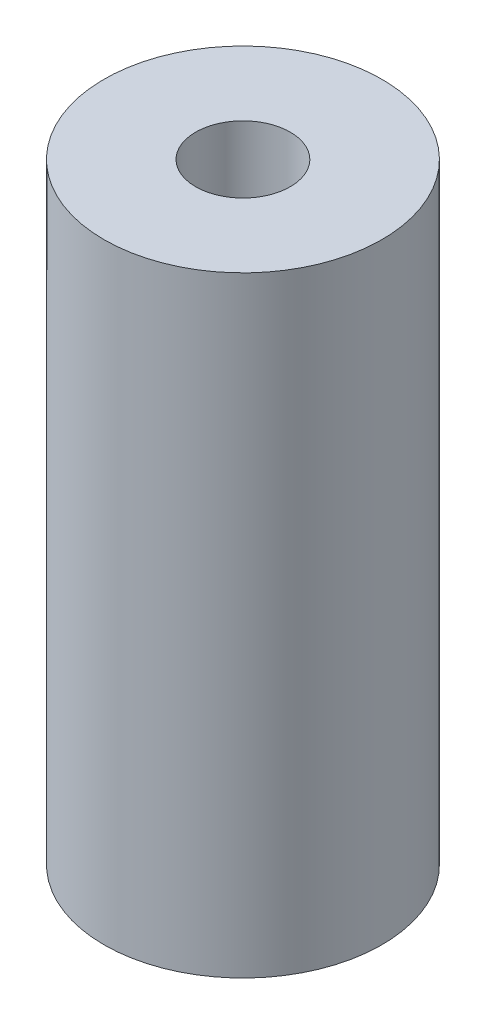
SolidWorks part; units mm, degrees
ref_plane "Front Plane" through (0, 0, 0) normal (0, 0, 1) x (1, 0, 0)
ref_plane "Top Plane" through (0, 0, 0) normal (0, 1, 0) x (1, 0, 0)
ref_plane "Right Plane" through (0, 0, 0) normal (1, 0, 0) x (0, 0, -1)
sketch "Sketch1" plane through (0, 0, 0) normal (0, 1, 0) x (1, 0, 0)
  circle A0 centre (0, 0) radius 1.55
  circle A1 centre (0, 0) radius 4.55
  dimension "D1" = 3.1
  dimension "D2" = 3
extrude "Boss-Extrude1" add sketch "Sketch1" along normal blind 20
